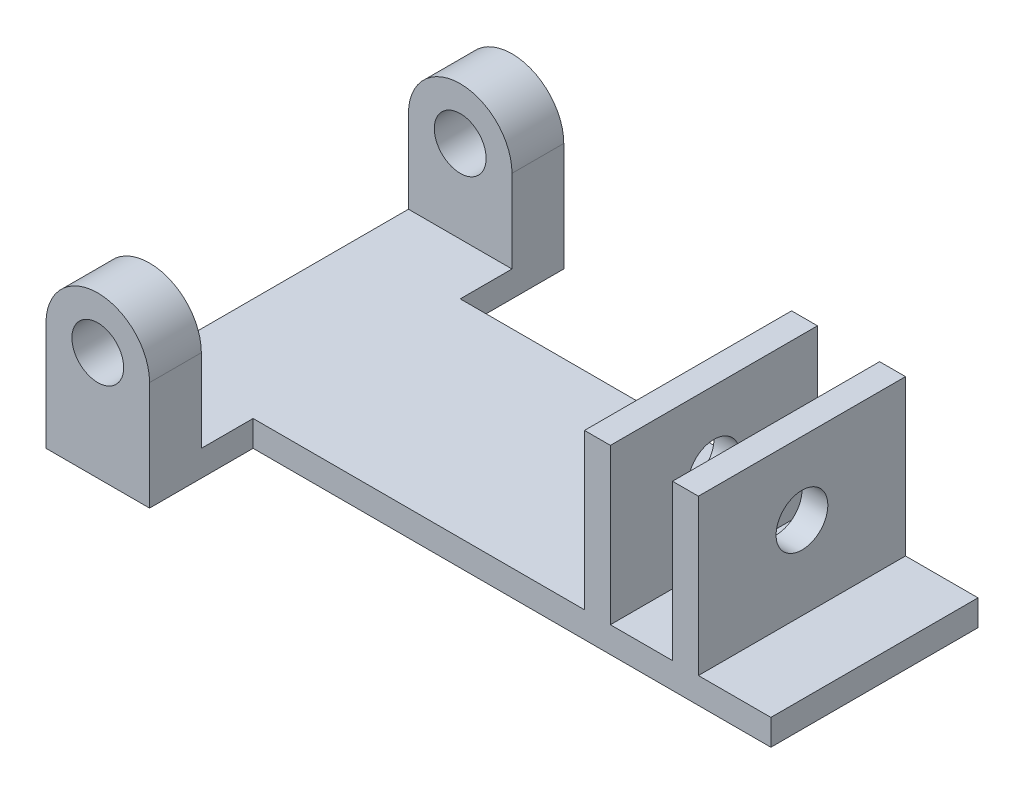
SolidWorks part; units mm, degrees
ref_plane "Front Plane" through (0, 0, 0) normal (0, 0, 1) x (1, 0, 0)
ref_plane "Top Plane" through (0, 0, 0) normal (0, 1, 0) x (1, 0, 0)
ref_plane "Right Plane" through (0, 0, 0) normal (1, 0, 0) x (0, 0, -1)
sketch "Sketch1" plane through (0, 0, 0) normal (0, 1, 0) x (1, 0, 0)
  line L1 (-12.7, 0) -> (0, 0)
  line L2 (-12.7, 0) -> (-12.7, 50.8)
  line L3 (-12.7, 50.8) -> (0, 50.8)
  line L4 (0, 0) -> (0, 50.8)
  line L5 (-12.7, 0) -> (0, 50.8) construction
  line L6 (-12.7, 50.8) -> (0, 0) construction
  point P0 (-6.35, 25.4)
  point P6 (0, 0)
  dimension "D1" = 12.7
  dimension "D2" = 50.8
extrude "Base Extrude" add sketch "Sketch1" along normal blind 3.175
sketch "Sketch6" plane through (0, 3.175, 0) normal (0, 1, 0) x (1, 0, 0)
  line L0 (0, 0) -> (0, 50.8) construction
  line L1 (-12.7, 0) -> (0, 0)
  line L2 (-12.7, 0) -> (-12.7, 6.35)
  line L3 (-12.7, 6.35) -> (0, 6.35)
  line L4 (0, 0) -> (0, 6.35)
  dimension "D1" = 6.35
extrude "Arch Base Extrude" add sketch "Sketch6" along normal blind 10.16
ref_plane "Arch Mirror Plane" through (0, 0, -25.4) normal (0, 0, 1) x (1, 0, 0)
mirror "Mirror Arch Base" about plane through (0, 0, -25.4) normal (0, 0, 1) of "Arch Base Extrude"
sketch "Sketch2" plane through (0, 0, 0) normal (0, 0, 1) x (1, 0, 0)
  line L1 (-12.7, 13.335) -> (0, 13.335)
  arc A1 (-12.7, 13.335) -> (0, 13.335) centre (-6.35, 13.335) cw
  point P5 (0, 0)
extrude "Arch Extrude" add sketch "Sketch2" against normal blind 6.35
sketch "Sketch3" plane through (0, 0, 0) normal (0, 0, 1) x (1, 0, 0)
  line L0 (-12.7, 0) -> (0, 0) construction
  circle A0 centre (-6.35, 13.335) radius 3.175
  arc A1 (0, 13.335) -> (-12.7, 13.335) centre (-6.35, 13.335) ccw construction
  point P2 (0, 0)
  point P5 (-6.35, 0)
  point P9 (-6.35, 19.685)
  dimension "D1" = 6.35
  dimension "D2" = 6.35
extrude "Arch Hole Cut" cut sketch "Sketch3" against normal up to surface (6.35 mm away) up to face at (-6.35, 9.8425, -6.35)
mirror "Mirror Arch and Hole" about plane through (0, 0, -25.4) normal (0, 0, 1) of "Arch Extrude", "Arch Hole Cut"
sketch "Sketch4" plane through (0, 0, 0) normal (1, 0, 0) x (0, 0, -1)
  line L0 (6.35, 3.175) -> (44.45, 3.175) construction
  line L1 (12.7, 3.175) -> (38.1, 3.175)
  line L2 (12.7, 3.175) -> (12.7, 0)
  line L3 (12.7, 0) -> (38.1, 0)
  line L4 (38.1, 3.175) -> (38.1, 0)
  line L5 (0, 0) -> (50.8, 0) construction
  point P8 (25.4, 0)
  dimension "D1" = 25.4
extrude "Tab Extrude" add sketch "Sketch4" along normal blind 63.5
sketch "Sketch5" plane through (0, 3.175, 0) normal (0, 1, 0) x (1, 0, 0)
  line L0 (63.5, 38.1) -> (0, 38.1) construction
  line L1 (40.64, 38.1) -> (43.815, 38.1)
  line L2 (40.64, 38.1) -> (40.64, 12.7)
  line L3 (40.64, 12.7) -> (43.815, 12.7)
  line L4 (43.815, 38.1) -> (43.815, 12.7)
  line L5 (63.5, 12.7) -> (0, 12.7) construction
  line L6 (0, 6.35) -> (0, 12.7) construction
  line L8 (54.61, 38.1) -> (51.435, 38.1)
  line L9 (54.61, 38.1) -> (54.61, 12.7)
  line L10 (54.61, 12.7) -> (51.435, 12.7)
  line L11 (51.435, 38.1) -> (51.435, 12.7)
  dimension "D1" = 40.64
  dimension "D2" = 3.175
  dimension "D3" = 3.175
  dimension "D4" = 7.62
extrude "Square Slide Guides Extrude" add sketch "Sketch5" along normal blind 19.05
sketch "Sketch14" plane through (54.61, 0, 0) normal (1, 0, 0) x (0, 0, -1)
  line L0 (12.7, 3.175) -> (38.1, 3.175) construction
  circle A0 centre (25.4, 13.335) radius 3.175
  point P4 (25.4, 3.175)
  dimension "D2" = 6.35
  dimension "D1" = 10.16
extrude "Cut-Extrude3" cut sketch "Sketch14" against normal up to surface (13.97 mm away) up to face at (40.64, 12.7, -25.4)
